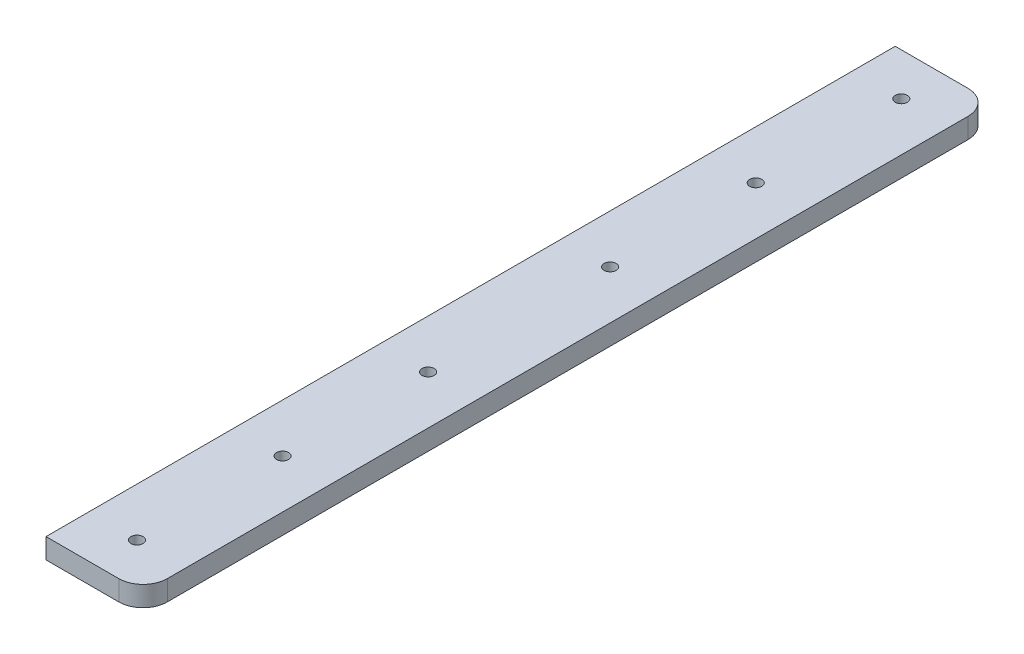
SolidWorks part; units mm, degrees
ref_plane "Front Plane" through (0, 0, 0) normal (0, 0, 1) x (1, 0, 0)
ref_plane "Top Plane" through (0, 0, 0) normal (0, 1, 0) x (1, 0, 0)
ref_plane "Right Plane" through (0, 0, 0) normal (1, 0, 0) x (0, 0, -1)
sketch "Sketch1" plane through (0, 0, 0) normal (0, 1, 0) x (1, 0, 0)
  line L4 (-12, -105) -> (-12, 105)
  line L13 (-12, 105) -> (6, 105)
  line L14 (12, 99) -> (12, -99)
  line L15 (6, -105) -> (-12, -105)
  line L16 (0, 105) -> (0, -105) construction
  arc A43 (6, -105) -> (12, -99) centre (6, -99) ccw
  arc A44 (12, 99) -> (6, 105) centre (6, 99) ccw
  circle A45 centre (0, -94.5) radius 1.5
  circle A46 centre (0, -58.5) radius 1.5
  circle A47 centre (0, -22.5) radius 1.5
  circle A71 centre (0, 94.5) radius 1.5
  circle A72 centre (0, 58.5) radius 1.5
  circle A73 centre (0, 22.5) radius 1.5
  dimension "D5" = 36
  dimension "D10" = 24
  dimension "D11" = 6
  dimension "D15" = 3
  dimension "D17" = 36
  dimension "D12" = 3
  dimension "D4" = 22.5
  dimension "D2" = 210
  dimension "D3" = 45
  dimension "D6" = 36
  dimension "D8" = 12
extrude "Boss-Extrude1" add sketch "Sketch1" along normal blind 5
